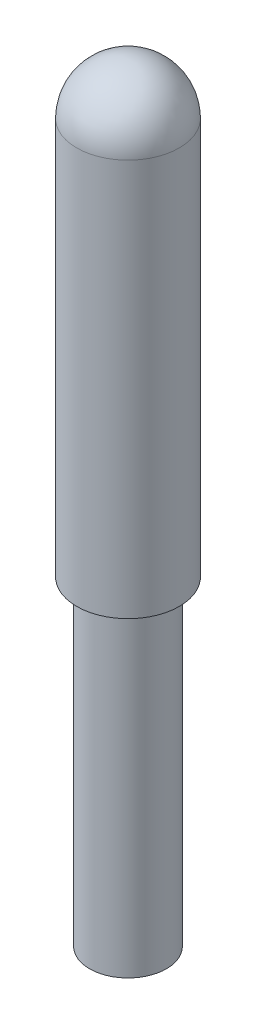
SolidWorks part; units mm, degrees
ref_plane "Front Plane" through (0, 0, 0) normal (0, 0, 1) x (1, 0, 0)
ref_plane "Top Plane" through (0, 0, 0) normal (0, 1, 0) x (1, 0, 0)
ref_plane "Right Plane" through (0, 0, 0) normal (1, 0, 0) x (0, 0, -1)
sketch "Sketch1" plane through (0, 0, 0) normal (0, 1, 0) x (1, 0, 0)
  circle A0 centre (0, 0) radius 4
  circle A1 centre (0, 0) radius 3
  dimension "D1" = 8
  dimension "D2" = 1
extrude "Boss-Extrude1" add sketch "Sketch1" along normal blind 35 contours A0 | A1 A0 | A0 | A1 region at (-3.8869, 0, 0) region at (0, 0, 0)
extrude "Boss-Extrude2" add sketch "Sketch1<3>" against normal blind 25 contours A1 region at (0, 0, 0)
sketch "Sketch1<3>" plane through (0, 0, 0) normal (0, 1, 0) x (1, 0, 0) same geometry as "Sketch1"
fillet "Fillet1" radius 4 1 edges at (0, 35, 4)
